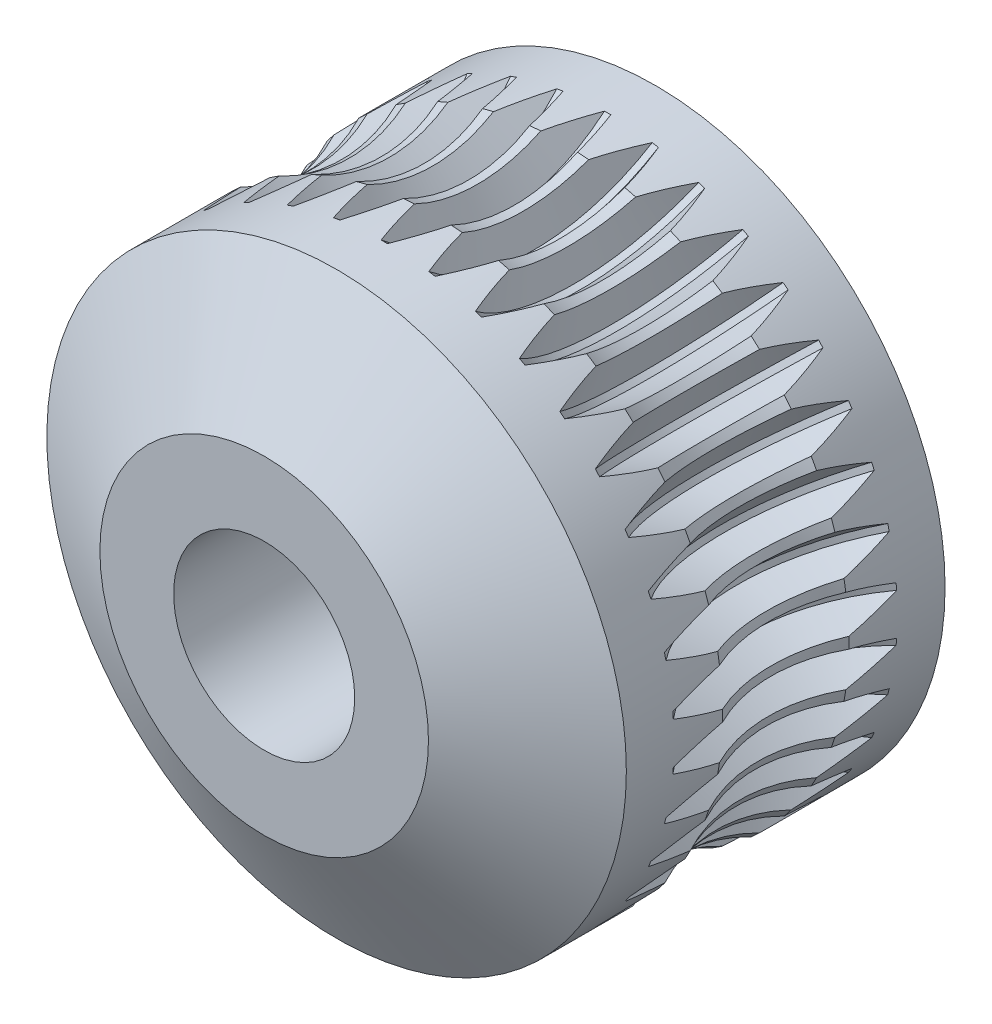
SolidWorks part; units mm, degrees
ref_plane "Front Plane" through (0, 0, 0) normal (0, 0, 1) x (1, 0, 0)
ref_plane "Top Plane" through (0, 0, 0) normal (0, 1, 0) x (1, 0, 0)
ref_plane "Right Plane" through (0, 0, 0) normal (1, 0, 0) x (0, 0, -1)
sketch "Sketch1" plane through (0, 0, 0) normal (0, 0, 1) x (1, 0, 0)
  circle A0 centre (0, 0) radius 4
  circle A1 centre (0, 0) radius 1.25
  dimension "D1" = 8
  dimension "D2" = 2.5
extrude "Boss-Extrude1" add sketch "Sketch1" along normal blind 6.4
chamfer "Chamfer1" distance 1 angle 60 1 edges at (4, 0, 6.4) first distance on face at (4, 0, 6.4)
ref_plane "Plane1" through (0, 0, 3.2) normal (0, 0, -1) x (-1, 0, 0)
sketch "Sketch2" plane through (0, 0, 0) normal (1, 0, 0) x (0, 0, -1)
  line L0 (-3.2, -3.3) -> (-3.2, 3.3) construction
  line L1 (0, 0) -> (-12.0979, 0) construction
  circle A0 centre (-3.2, 5.8) radius 2
  dimension "D1" = 4
  dimension "D2" = 5.8
revolve "Cut-Revolve1" cut sketch "Sketch2" angle 360 about L1
sketch "Sketch3" plane through (3.2, 0, 3.2) normal (0, 0, 1) x (1, 0, 0)
  line L0 (-3.2, 3.43) -> (-3.2, 3.8) construction
  line L1 (-3.4574, 3.8) -> (-2.9426, 3.8) construction
  line L2 (-5.0425, 5.8) -> (-2.1511, 5.8) construction
  line L3 (-3.2437, 3.43) -> (-3.1562, 3.43)
  line L4 (-3.1562, 3.43) -> (-2.9426, 3.8)
  line L5 (-2.9426, 3.8) -> (-2.1511, 3.8)
  line L6 (-2.1511, 3.8) -> (-2.1511, 4.3976)
  line L7 (-2.1511, 4.3976) -> (-4.2489, 4.3976)
  line L8 (-4.2489, 4.3976) -> (-4.2489, 3.8)
  line L9 (-4.2489, 3.8) -> (-3.4574, 3.8)
  line L10 (-3.4574, 3.8) -> (-3.2437, 3.43)
  point P15 (-3.2, 0)
  dimension "D1" = 2
  dimension "D2" = 5.8
  dimension "D3" = 0.0875
  dimension "D4" = 0.37
  dimension "D5" = 60
revolve "Cut-Revolve2" cut sketch "Sketch3" angle 360 about L2
ref_axis "Axis1" through (0, 0, 6.4) along (0, 0, -1)
pattern_circular "CirPattern1" count 38 over 360 about axis through (0, 0, 6.4) along (0, 0, -1) of "Cut-Revolve2"
chamfer "Chamfer2" distance 1 angle 60 1 edges at (4, 0, 0) first distance on face at (0, 0, 1.9934)
equation "\"D2@Sketch2\"=(7.6+4)/2"
